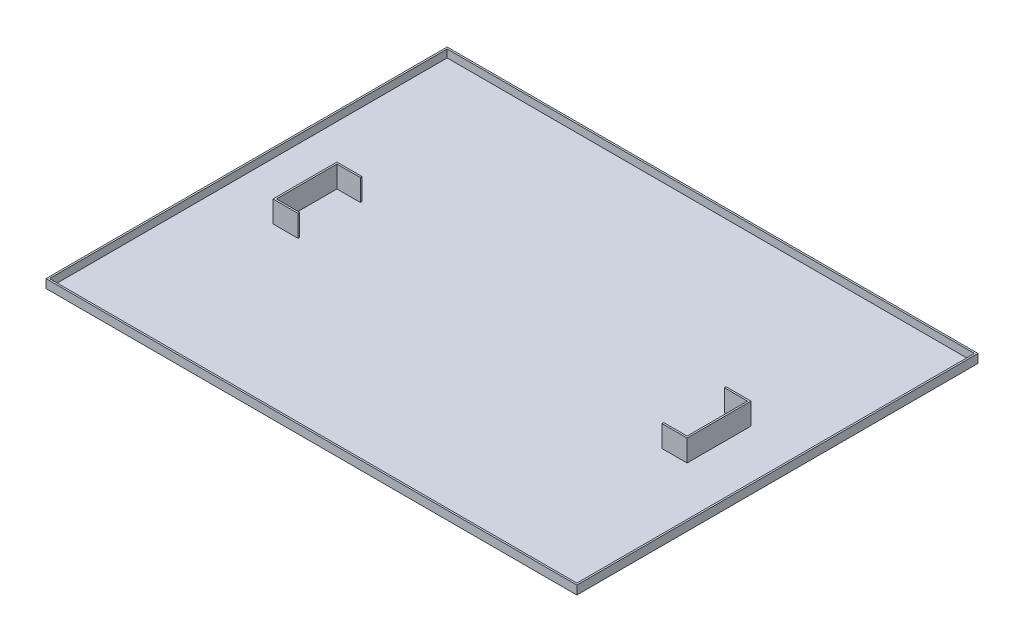
SolidWorks part; units mm, degrees
ref_plane "Front Plane" through (0, 0, 0) normal (0, 0, 1) x (1, 0, 0)
ref_plane "Top Plane" through (0, 0, 0) normal (0, 1, 0) x (1, 0, 0)
ref_plane "Right Plane" through (0, 0, 0) normal (1, 0, 0) x (0, 0, -1)
sketch "Sketch1" plane through (0, 0, 0) normal (0, 1, 0) x (1, 0, 0)
  line L0 (-3070, -2320) -> (-3070, 2320)
  line L1 (-3050, -2300) -> (3050, -2300)
  line L2 (-3050, -2300) -> (-3050, 2300)
  line L3 (-3050, 2300) -> (3050, 2300)
  line L4 (3050, -2300) -> (3050, 2300)
  line L5 (-3050, -2300) -> (3050, 2300) construction
  line L6 (-3050, 2300) -> (3050, -2300) construction
  line L7 (-3070, 2320) -> (3070, 2320)
  line L8 (3070, -2320) -> (3070, 2320)
  line L9 (-3070, -2320) -> (3070, -2320)
  point P0 (0, 0)
  dimension "D1" = 6100
  dimension "D2" = 4600
  dimension "D3" = 20
extrude "Boss-Extrude1" add sketch "Sketch1" along normal blind 100
extrude "Boss-Extrude2" add sketch "Sketch1<2>" along normal blind 10 contours L1 L4 L3 L2 region at (0, 0, 0)
sketch "Sketch1<2>" plane through (0, 0, 0) normal (0, 1, 0) x (1, 0, 0) same geometry as "Sketch1"
sketch "Sketch2" plane through (0, 10, 0) normal (0, 1, 0) x (1, 0, 0)
  line L0 (-2395, 370) -> (-2105, 370)
  line L1 (-2375, 350) -> (-2125, 350)
  line L2 (-2375, 350) -> (-2375, -350)
  line L3 (-2375, -350) -> (-2125, -350)
  line L5 (-2375, 350) -> (-2125, -350) construction
  line L6 (-2375, -350) -> (-2125, 350) construction
  line L7 (-2105, 370) -> (-2105, 350)
  line L8 (-2395, -370) -> (-2105, -370)
  line L9 (-2395, 370) -> (-2395, -370)
  line L10 (-2125, 350) -> (-2105, 350)
  line L11 (-2125, -350) -> (-2105, -350)
  line L12 (-2105, -350) -> (-2105, -370)
  line L13 (-2125, 350) -> (-2125, -350) construction
  line L14 (-2105, 370) -> (-2105, -370) construction
  point P0 (-2250, 0)
  dimension "D1" = 700
  dimension "D2" = 250
  dimension "D4" = 2250
  dimension "D3" = 20
extrude "Boss-Extrude3" add sketch "Sketch2" along normal blind 250
mirror "Mirror1" about plane through (0, 0, 0) normal (1, 0, 0) of "Boss-Extrude3"
